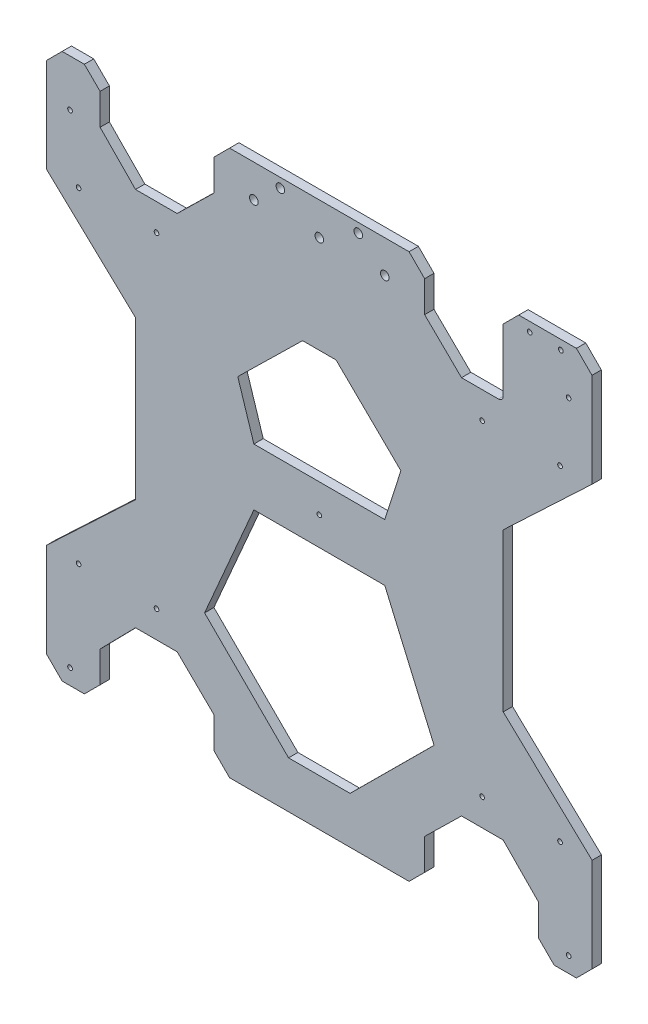
SolidWorks part; units mm, degrees
material "6063-T5"
ref_plane "Piano frontale" through (0, 0, 0) normal (0, 0, 1) x (1, 0, 0)
ref_plane "Piano superiore" through (0, 0, 0) normal (0, 1, 0) x (1, 0, 0)
ref_plane "Piano destro" through (0, 0, 0) normal (1, 0, 0) x (0, 0, -1)
sketch "Schizzo13" plane through (0, 0, 0) normal (0, 0, 1) x (1, 0, 0)
  line L0 (175, 350) -> (175, 0) construction
  line L1 (9.9192, 0) -> (24.2012, 0)
  line L2 (-0.0808, 279.5) -> (57, 225.6111)
  line L3 (217, 193.2869) -> (227.343, 225.6111)
  line L4 (133, 193.2869) -> (217, 193.2869)
  line L5 (350, 175) -> (0, 175) construction
  line L6 (-60.1887, 10) -> (461.2643, 10) construction
  line L7 (279.5, 279.5) -> (279.5, 175) construction
  line L8 (-12.961, 344) -> (386.8832, 344) construction
  line L9 (-12.961, 329) -> (386.8832, 329) construction
  line L11 (279.5, 70.5) -> (175, 70.5) construction
  line L12 (70.5, 70.5) -> (175, 70.5) construction
  line L15 (70.5, 279.5) -> (169.5845, 279.5) construction
  line L16 (175, 279.5) -> (329.5, 279.5) construction
  line L17 (329.5, 70.5) -> (329.5, 279.5) construction
  line L18 (20.5, 70.5) -> (329.5, 70.5) construction
  line L19 (20.5, 70.5) -> (20.5, 279.5) construction
  line L20 (175, 279.5) -> (20.5, 279.5) construction
  line L21 (15, -40.9714) -> (15, 408.5301) construction
  line L22 (335, -40.9714) -> (335, 408.5301) construction
  line L23 (-12.961, 320) -> (386.8832, 320) construction
  line L24 (9.9192, 0) -> (-0.0808, 10)
  line L25 (340, 0) -> (350, 10)
  line L26 (107.4046, 340) -> (107.4046, 320)
  line L27 (107.4046, 320) -> (83.7454, 296.8073)
  line L28 (70.5, 279.5) -> (20.5, 279.5) construction
  line L29 (57.0174, 296.8073) -> (34.282, 320)
  line L30 (83.7454, 296.8073) -> (57.0174, 296.8073)
  line L31 (34.282, 320) -> (34.282, 340)
  line L32 (24.2012, 350) -> (9.9192, 350)
  line L33 (133, 193.2869) -> (122.657, 225.6111)
  line L35 (164.2491, 266.3832) -> (185.7509, 266.3832)
  line L36 (122.657, 225.6111) -> (164.2491, 266.3832)
  line L37 (57, 225.6111) -> (57, 175)
  line L38 (227.343, 225.6111) -> (185.7509, 266.3832)
  line L39 (293, 225.6111) -> (293, 124.3889)
  line L40 (350.0808, 279.5) -> (293, 225.6111)
  line L44 (292.9826, 299.8073) -> (292.9826, 340)
  line L46 (117.4046, 0) -> (232.5954, 0)
  line L47 (266.2546, 296.8073) -> (289.9826, 296.8073)
  line L48 (242.5954, 320) -> (266.2546, 296.8073)
  line L49 (242.5954, 340) -> (242.5954, 320)
  line L50 (350.0808, 70.5) -> (293, 124.3889)
  line L53 (350, 10) -> (350.0808, 70.5)
  line L55 (315.718, 30) -> (315.718, 10)
  line L56 (292.9826, 53.1927) -> (315.718, 30)
  line L57 (266.2546, 53.1927) -> (292.9826, 53.1927)
  line L58 (242.5954, 30) -> (266.2546, 53.1927)
  line L59 (242.5954, 10) -> (242.5954, 30)
  line L60 (107.4046, 10) -> (107.4046, 30)
  line L61 (107.4046, 30) -> (83.7454, 53.1927)
  line L62 (83.7454, 53.1927) -> (57.0174, 53.1927)
  line L63 (57.0174, 53.1927) -> (34.282, 30)
  line L64 (34.282, 30) -> (34.2012, 10)
  line L66 (-0.0808, 10) -> (-0.0808, 70.5)
  line L69 (-0.0808, 70.5) -> (57, 124.3889)
  line L70 (57, 124.3889) -> (57, 175)
  line L71 (-0.0808, 279.5) -> (-0.0808, 340)
  line L72 (117.4046, 350) -> (232.5954, 350)
  line L73 (302.9826, 350) -> (340, 350)
  line L74 (350.0808, 279.5) -> (350, 340)
  line L75 (325.718, 0) -> (340, 0)
  line L76 (24.2012, 0) -> (34.2012, 10)
  line L77 (117.4046, 0) -> (107.4046, 10)
  line L78 (232.5954, 0) -> (242.5954, 10)
  line L79 (315.718, 10) -> (325.718, 0)
  line L80 (9.9192, 350) -> (-0.0808, 340)
  line L81 (24.2012, 350) -> (34.282, 340)
  line L82 (107.4046, 340) -> (117.4046, 350)
  line L83 (232.5954, 350) -> (242.5954, 340)
  line L84 (292.9826, 340) -> (302.9826, 350)
  line L85 (340, 350) -> (350, 340)
  line L86 (133, 156.7131) -> (101.3482, 83.6168)
  line L87 (101.3482, 83.6168) -> (155.2542, 30)
  line L88 (155.2542, 30) -> (194.7458, 30)
  line L89 (133, 156.7131) -> (217, 156.7131)
  line L90 (248.6518, 83.6168) -> (194.7458, 30)
  line L91 (217, 156.7131) -> (248.6518, 83.6168)
  circle A0 centre (15, 320) radius 1.5
  circle A1 centre (20.5, 279.5) radius 1.5
  circle A2 centre (70.5, 279.5) radius 1.5
  circle A3 centre (175, 175) radius 1.5
  arc A4 (289.9826, 296.8073) -> (292.9826, 299.8073) centre (289.9826, 299.8073) ccw
  circle A5 centre (20.5, 70.5) radius 1.5
  circle A6 centre (200, 344) radius 2.75
  circle A7 centre (150, 344) radius 2.75
  circle A8 centre (175, 329) radius 2.75
  circle A9 centre (217, 329) radius 2.75
  circle A10 centre (133, 329) radius 2.75
  circle A11 centre (70.5, 70.5) radius 1.5
  circle A12 centre (279.5, 70.5) radius 1.5
  circle A13 centre (329.5, 70.5) radius 1.5
  circle A14 centre (335, 10) radius 1.5
  circle A15 centre (15, 10) radius 1.5
  circle A16 centre (279.5, 279.5) radius 1.5
  circle A17 centre (329.5, 279.5) radius 1.5
  circle A18 centre (335, 320) radius 1.5
  circle A19 centre (310, 344) radius 1.5
  circle A20 centre (330, 344) radius 1.5
  point P7 (175, 175)
  point P25 (175, 344)
  point P30 (175, 329)
  point P41 (175, 175)
  point P43 (329.5, 175)
  point P46 (15, 320)
  point P54 (335, 320)
  point P55 (335, 10)
  point P56 (15, 10)
  point P57 (15, 320)
  point P58 (335, 320)
  point P59 (15, 10)
  point P60 (335, 10)
  point P93 (292.9826, 296.8073)
  point P155 (175, 156.7131)
  point P156 (175, 30)
  dimension "D5" = 42
  dimension "D6" = 5.5
  dimension "D7" = 25
  dimension "D8" = 15
  dimension "D10" = 154.5
  dimension "D3" = 104.5
  dimension "D17" = 20
  dimension "D2" = 3
  dimension "D4" = 104.5
  dimension "D9" = 175
  dimension "D11" = 104.5
  dimension "D12" = 279.5
  dimension "D13" = 104.5
  dimension "D15" = 310
  dimension "D16" = 320
extrude "Estrusione-Estrusione2" add sketch "Schizzo13" against normal blind 6
sketch "Schizzo14" plane through (0, 0, 0) normal (0, 0, 1) x (1, 0, 0)
  line L0 (350, 350) -> (0, 350)
  line L1 (232.5954, 350) -> (117.4046, 350) construction
  line L2 (0, 350) -> (0, 0)
  line L3 (0, 0) -> (350, 0)
  line L4 (117.4046, 0) -> (232.5954, 0) construction
  line L5 (175, 350) -> (175, 0) construction
  line L6 (350, 350) -> (350, 0)
  circle A0 centre (175, 223.4858) radius 4.4409
  circle A1 centre (175, 78.9698) radius 4.6362
sketch "Schizzo15" plane through (0, 0, 0) normal (0, 0, 1) x (1, 0, 0)
  text T0 "HackerBot" font "Lobster 1.4" height 14
